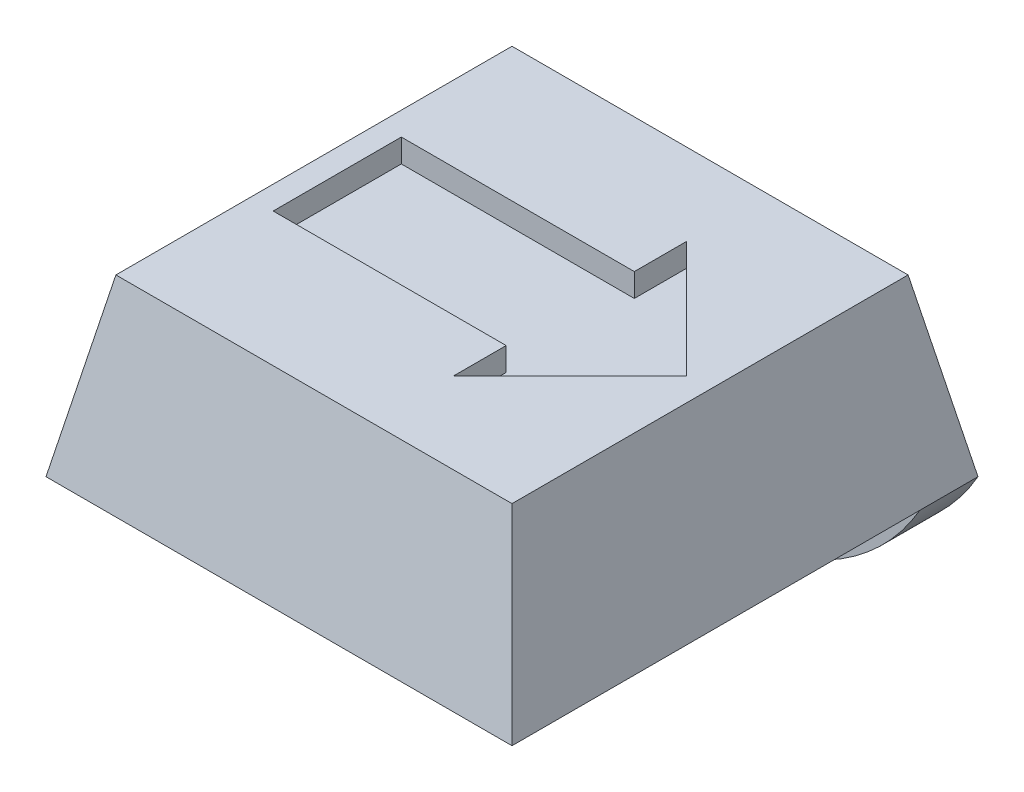
SolidWorks part; units mm, degrees
ref_plane "Front Plane" through (0, 0, 0) normal (0, 0, 1) x (1, 0, 0)
ref_plane "Top Plane" through (0, 0, 0) normal (0, 1, 0) x (1, 0, 0)
ref_plane "Right Plane" through (0, 0, 0) normal (1, 0, 0) x (0, 0, -1)
sketch "Sketch1" plane through (0, 0, 0) normal (0, 1, 0) x (1, 0, 0)
  line L1 (0, 0) -> (8, 0)
  line L2 (0, 0) -> (0, 8)
  line L3 (0, 8) -> (8, 8)
  line L4 (8, 0) -> (8, 8)
  dimension "D1" = 8
  dimension "D2" = 8
extrude "Boss-Extrude1" add sketch "Sketch1" along normal blind 3
sketch "Sketch2" plane through (0, 0, 0) normal (0, 0, 1) x (1, 0, 0)
  line L0 (0, 0) -> (0.6, 3)
  line L1 (0, 3) -> (8, 3) construction
  line L2 (0.6, 3) -> (0, 3)
  line L3 (0, 3) -> (0, 0)
  line L4 (8, 0) -> (7.4, 3)
  line L5 (7.4, 3) -> (8, 3)
  line L6 (8, 3) -> (8, 0)
  dimension "D1" = 0.6
  dimension "D2" = 0.6
extrude "Cut-Extrude1" cut sketch "Sketch2" against normal through all both and the other way through all
sketch "Sketch3" plane through (0, 0, 0) normal (1, 0, 0) x (0, 0, -1)
  line L0 (0, 0) -> (0.6, 3)
  line L1 (8, 3) -> (0, 3) construction
  line L2 (0.6, 3) -> (0, 3)
  line L3 (0, 3) -> (0, 0)
  line L4 (8, 3) -> (7.4, 3)
  line L5 (7.4, 3) -> (8, 0)
  line L6 (8, 3) -> (8, 0)
  dimension "D1" = 0.6
  dimension "D2" = 0.6
extrude "Cut-Extrude2" cut sketch "Sketch3" along normal blind 11
sketch "Sketch4" plane through (0, 0, 0) normal (0, -1, 0) x (1, 0, 0)
  line L0 (8, 0) -> (8, -8) construction
  line L3 (0, 0) -> (8, 0) construction
  circle A0 centre (4, -3.75) radius 1.8
  dimension "D1" = 3.6
  dimension "D2" = 4
  dimension "D3" = 3.75
extrude "Cut-Extrude3" cut sketch "Sketch4" against normal blind 0.8
sketch "Sketch5" plane through (0, 0, 0) normal (0, -1, 0) x (1, 0, 0)
  line L0 (8, 0) -> (8, -8) construction
  line L1 (0, -8) -> (8, -8)
  line L2 (0, -8) -> (0, -7)
  line L3 (0, -7) -> (8, -7)
  line L4 (8, -8) -> (8, -7)
  dimension "D1" = 1
extrude "Boss-Extrude2" add sketch "Sketch5" along normal blind 2
fillet "Fillet1" radius 4 2 edges at (8, -2, -7.5) (0, -2, -7.5)
sketch "Sketch6" plane through (0, 3, 0) normal (0, 1, 0) x (1, 0, 0)
  line L0 (5, 5.1) -> (5, 6)
  line L1 (1, 5.1) -> (5, 5.1)
  line L2 (1, 5.1) -> (1, 2.9)
  line L3 (1, 2.9) -> (5, 2.9)
  line L4 (5, 5.1) -> (5, 2.9)
  line L5 (5, 6) -> (7, 4)
  line L6 (7, 4) -> (5, 2)
  line L7 (5, 2) -> (5, 2.9)
  line L8 (7.4, 7.4) -> (0.6, 7.4) construction
  line L9 (7.4, 0.6) -> (0.6, 0.6) construction
  line L10 (7.4, 7.4) -> (7.4, 0.6) construction
  line L11 (0.6, 7.4) -> (0.6, 0.6) construction
  point P15 (7, 3.7765)
  point P16 (7.4, 4)
  dimension "D1" = 2.3
  dimension "D2" = 2.3
  dimension "D3" = 1.4
  dimension "D4" = 1.4
  dimension "D5" = 0.4
  dimension "D6" = 0.4
  dimension "D7" = 4
  dimension "D8" = 0
extrude "Cut-Extrude4" cut sketch "Sketch6" against normal blind 0.4 contours L4 L1 L2 L3 | L7 L6 L5 L0 L4 region at (3, 3, -4) region at (5.6667, 3, -4)
